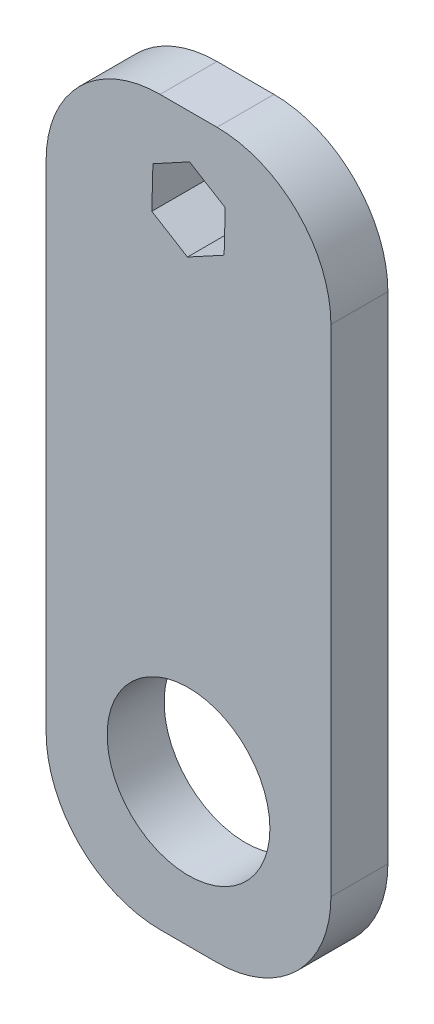
SolidWorks part; units mm, degrees
ref_plane "Front Plane" through (0, 0, 0) normal (0, 0, 1) x (1, 0, 0)
ref_plane "Top Plane" through (0, 0, 0) normal (0, 1, 0) x (1, 0, 0)
ref_plane "Right Plane" through (0, 0, 0) normal (1, 0, 0) x (0, 0, -1)
sketch "Sketch1" plane through (0, 0, 0) normal (0, 1, 0) x (1, 0, 0)
  line L1 (-25, -5) -> (25, -5)
  line L2 (-25, -5) -> (-25, 5)
  line L3 (-25, 5) -> (25, 5)
  line L4 (25, -5) -> (25, 5)
  line L5 (-25, -5) -> (25, 5) construction
  line L6 (-25, 5) -> (25, -5) construction
  point P0 (0, 0)
  dimension "D1" = 50
  dimension "D2" = 10
extrude "Boss-Extrude1" add sketch "Sketch1" along normal mid plane 127
sketch "Sketch2" plane through (0, 0, 5) normal (0, 0, 1) x (1, 0, 0)
  line L0 (0, -5.5) -> (0, 5.5) construction
  line L1 (6.2528, 44.6704) -> (6.4429, 52.0003)
  line L2 (6.4429, 52.0003) -> (0.1902, 55.8299)
  line L3 (0.1902, 55.8299) -> (-6.2528, 52.3296)
  line L4 (-6.2528, 52.3296) -> (-6.4429, 44.9997)
  line L5 (-6.4429, 44.9997) -> (-0.1902, 41.1701)
  line L6 (-0.1902, 41.1701) -> (6.2528, 44.6704)
  line L7 (-25, 63.5) -> (25, 63.5) construction
  line L8 (-25, -63.5) -> (25, -63.5) construction
  circle A0 centre (0, 48.5) radius 6.35 construction
  circle A2 centre (0, -38.5) radius 14.2875
  point P24 (0, 48.5)
  dimension "D1" = 15
  dimension "D2" = 25
extrude "Cut-Extrude1" cut sketch "Sketch2" against normal blind 127
fillet "Fillet1" radius 20 4 edges at (-25, -63.5, 0) (25, -63.5, 0) (25, 63.5, 0) (-25, 63.5, 0)
